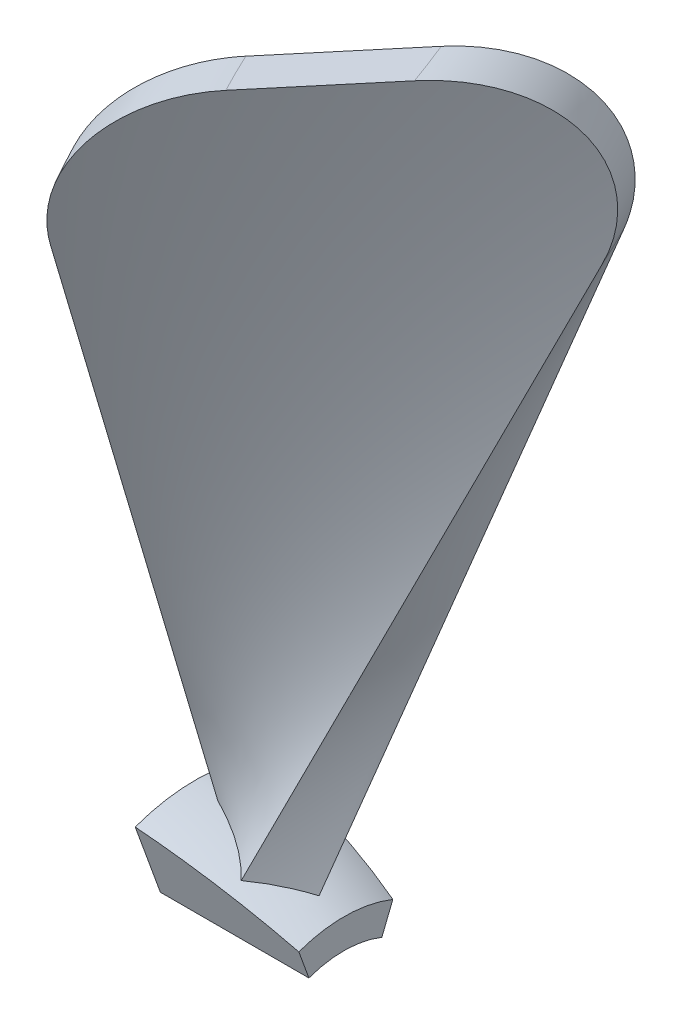
SolidWorks part; units mm, degrees
ref_plane "Спереди" through (0, 0, 0) normal (0, 0, 1) x (1, 0, 0)
ref_plane "Сверху" through (0, 0, 0) normal (0, 1, 0) x (1, 0, 0)
ref_plane "Справа" through (0, 0, 0) normal (1, 0, 0) x (0, 0, -1)
sketch "Эскиз2" plane through (0, 0, 0) normal (0, 0, 1) x (1, 0, 0)
  line L1 (1, 0) -> (28.5, 0)
  line L2 (-1000, 0) -> (49000, 0) construction
  line L3 (28.5, 0) -> (52.3107, 0)
  line L4 (1, 0) -> (1, 28.365)
  spline S0 degree 3 poles (1, 28.365) (21.4302, 25.4927) (38.5338, 16.0377) (52.3107, 0) knots 0.016012 0.016012 0.016012 0.016012 1 1 1 1
revolve "Повернуть1" add sketch "Эскиз2" angle 360 about L2
sketch "Эскиз3" plane through (0, 0, 0) normal (0, 1, 0) x (1, 0, 0)
  line L0 (-1000, 0) -> (49000, 0) construction
  line L1 (16.1294, 0.1091) -> (-47734.5616, -14827.9559) construction
  line L3 (-5.6255, -4.5523) -> (-47756.3165, -14832.6173) construction
  line L4 (14.9853, 1.848) -> (15.5785, -0.062)
  line L5 (15.5785, -0.062) -> (16.9582, 0.3664)
  line L6 (16.9582, 0.3664) -> (16.3651, 2.2764)
  line L7 (16.3651, 2.2764) -> (14.9853, 1.848)
ref_plane "Плоскость4" through (0, 0, 0) normal (0, -1, 0) x (-1, 0, 0)
ref_plane "Плоскость5" through (0, 140, 0) normal (0, -1, 0) x (-1, 0, 0)
sketch "Эскиз5" plane through (0, 140, 0) normal (0, 1, 0) x (1, 0, 0)
  line L0 (-134.8999, -185.4311) -> (-32274.2804, -38487.6532) construction
  line L1 (-134.5098, -195.1229) -> (-32273.8903, -38497.345) construction
  line L2 (-2.5137, -27.6594) -> (2.4875, -31.8558)
  line L3 (2.4875, -31.8558) -> (54.9167, 30.6269)
  line L4 (54.9167, 30.6269) -> (49.9155, 34.8233)
  line L5 (49.9155, 34.8233) -> (-2.5137, -27.6594)
ref_plane "Плоскость6" through (0, 10, 0) normal (0, -1, 0) x (-1, 0, 0)
ref_plane "Плоскость7" through (0, 20, 0) normal (0, -1, 0) x (-1, 0, 0)
sketch "Эскиз6" plane through (0, 20, 0) normal (0, -1, 0) x (-1, 0, 0)
  line L0 (-1030.8842, 1.4985) -> (48969.1158, 1.4985) construction
  line L1 (-18.9804, -3.0446) -> (-38321.2026, 32136.3359) construction
  line L2 (-27.9607, 20.7259) -> (-38330.1828, 32160.1063) construction
  line L3 (-12.9213, 8.1064) -> (-20.9156, -1.4208)
  line L4 (-20.9156, -1.4208) -> (-13.2926, -7.8172)
  line L5 (-13.2926, -7.8172) -> (-5.2984, 1.71)
  line L6 (-5.2984, 1.71) -> (-12.9213, 8.1064)
loft "По сечениям6" add profiles "Эскиз5", "Эскиз6" connector at (54.9167, 140, -30.6269) connector at (13.2926, 20, 7.8172)
fillet "Скругление3" radius 20 2 edges
sketch "Эскиз7" plane through (0, 0, 0) normal (-1, 0, 0) x (0, 0, 1)
  circle A0 centre (0, 0) radius 12.6
extrude "Вырез-Вытянуть1" cut sketch "Эскиз7" against normal blind 10
sketch "Эскиз8" plane through (0, 0, 0) normal (-1, 0, 0) x (0, 0, 1)
  circle A0 centre (0, 0) radius 16.5
extrude "Вырез-Вытянуть2" cut sketch "Эскиз8" against normal blind 2
sketch "Эскиз9" plane through (0, 0, 0) normal (-1, 0, 0) x (0, 0, 1)
  line L0 (0, 0) -> (-826.3977, 49931.3531) construction
  line L1 (-10.8982, 140) -> (6.264, 140) construction
  line L2 (-6.1484, 15.3117) -> (-11.896, 29.6251)
  line L3 (5.6385, 15.5067) -> (10.9112, 30.0076)
  line L6 (0, 0) -> (-18631.5746, 46398.9701) construction
  line L7 (0, 0) -> (17086.2457, 46990.0012) construction
  circle A0 centre (0, 0) radius 16.5 construction
  arc A2 (-11.896, 29.6251) -> (10.9112, 30.0076) centre (0.0098, -0.1265) ccw
  arc A3 (-6.1484, 15.3117) -> (5.6385, 15.5067) centre (0, 0) cw
  point P5 (-2.3171, 140)
extrude "Вырез-Вытянуть3" cut sketch "Эскиз9" against normal blind 25
sketch "Эскиз10" plane through (25, 0, 0) normal (-1, 0, 0) x (0, 0, 1)
  circle A0 centre (0, 0) radius 21.2536
extrude "Вырез-Вытянуть4" cut sketch "Эскиз10" against normal blind 40
